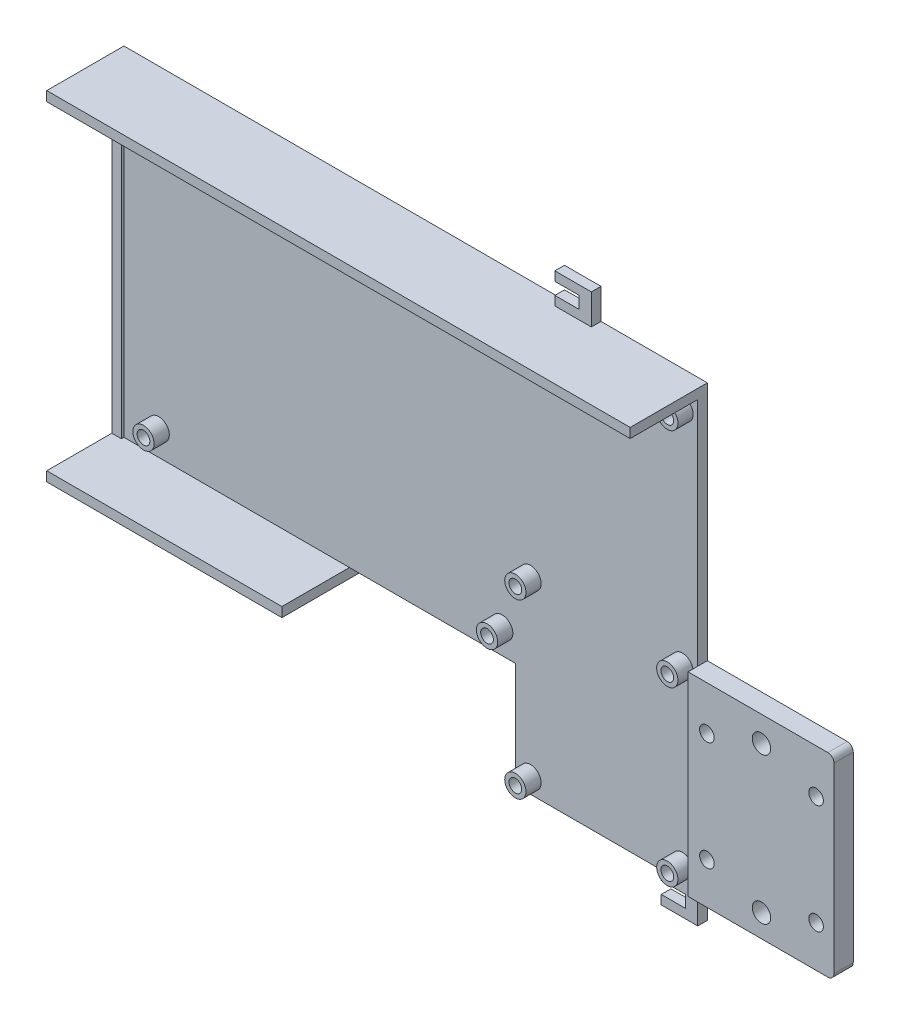
SolidWorks part; units mm, degrees
material "Custom Plastic"
ref_plane "X-Y Datum" through (0, 0, 0) normal (0, 0, 1) x (1, 0, 0)
ref_plane "X-Z Datum" through (0, 0, 0) normal (0, 1, 0) x (1, 0, 0)
ref_plane "Y-Z Datum" through (0, 0, 0) normal (1, 0, 0) x (0, 0, -1)
ref_plane "Plane1" through (-93.1675, 129.7126, -15.4932) normal (0, 1, 0) x (1, 0, 0)
sketch "Sketch2" plane through (0, 0, -17.0883) normal (0, 0, -1) x (-1, 0, 0)
  circle A0 centre (207.2845, 69.3586) radius 2.1 construction
  circle A1 centre (207.2845, 162.3226) radius 2.1 construction
  circle A2 centre (94.2545, 162.3226) radius 2.1 construction
  circle A3 centre (84.9365, 161.3866) radius 2.0955 construction
  circle A4 centre (94.2545, 69.3586) radius 2.1 construction
  circle A5 centre (84.9365, 88.1366) radius 2.0955 construction
  circle A6 centre (84.9365, 31.3866) radius 2.0955 construction
  circle A7 centre (34.9365, 31.3866) radius 2.0955 construction
  circle A8 centre (34.9365, 88.1366) radius 2.0955 construction
  circle A9 centre (34.9365, 161.3866) radius 2.0955 construction
  circle A10 centre (207.2845, 69.3586) radius 2.1
  circle A11 centre (207.2845, 162.3226) radius 2.1
  circle A12 centre (94.2545, 162.3226) radius 2.1
  circle A13 centre (84.9365, 161.3866) radius 2.0955
  circle A14 centre (94.2545, 69.3586) radius 2.1
  circle A15 centre (84.9365, 88.1366) radius 2.0955
  circle A16 centre (84.9365, 31.3866) radius 2.0955
  circle A17 centre (34.9365, 31.3866) radius 2.0955
  circle A18 centre (34.9365, 88.1366) radius 2.0955
  circle A19 centre (34.9365, 161.3866) radius 2.0955
  circle A20 centre (34.9365, 161.3866) radius 3.5
  circle A21 centre (84.9365, 161.3866) radius 3.5
  circle A22 centre (94.2545, 162.3226) radius 3.5
  circle A23 centre (207.2845, 162.3226) radius 3.5
  circle A24 centre (34.9365, 88.1366) radius 3.5
  circle A25 centre (34.9365, 31.3866) radius 3.5
  circle A26 centre (84.9365, 31.3866) radius 3.5
  circle A27 centre (84.9365, 88.1366) radius 3.5
  circle A28 centre (94.2545, 69.3586) radius 3.5
  circle A29 centre (207.2845, 69.3586) radius 3.5
  dimension "D1" = 7
  dimension "D2" = 7
  dimension "D3" = 7
  dimension "D4" = 7
extrude "Boss-Extrude1" add sketch "Sketch2" along normal blind 5
sketch "Sketch3" plane through (0, 0, -22.0883) normal (0, 0, -1) x (-1, 0, 0)
  line L1 (29.9365, 166.3866) -> (218.7145, 166.3866)
  line L2 (29.9365, 166.3866) -> (29.9365, 61.2306)
  line L3 (89.9365, 61.2306) -> (218.7145, 61.2306)
  line L4 (218.7145, 166.3866) -> (218.7145, 61.2306)
  line L6 (29.9365, 61.2306) -> (29.9365, 26.3866)
  line L7 (29.9365, 26.3866) -> (89.9365, 26.3866)
  line L8 (89.9365, 61.2306) -> (89.9365, 26.3866)
extrude "Boss-Extrude2" add sketch "Sketch3" along normal blind 3.175
sketch "Sketch4" plane through (0, 0, -25.2633) normal (0, 0, -1) x (-1, 0, 0)
  line L0 (29.9365, 166.3866) -> (29.9365, 169.5616)
  line L1 (144.5201, 58.0556) -> (144.5201, 61.2306)
  line L2 (89.9365, 61.2306) -> (218.7145, 61.2306) construction
  line L3 (218.7145, 166.3866) -> (221.8895, 166.3866)
  line L4 (218.7145, 61.2306) -> (221.8895, 61.2306)
  line L12 (26.7615, 169.5616) -> (26.7615, 23.2116)
  line L13 (26.7615, 23.2116) -> (93.1115, 23.2116)
  line L14 (93.1115, 23.2116) -> (93.1115, 58.0556)
  line L15 (93.1115, 58.0556) -> (221.8895, 58.0556)
  line L16 (221.8895, 58.0556) -> (221.8895, 169.5616)
  line L17 (221.8895, 169.5616) -> (26.7615, 169.5616)
  line L18 (26.7615, 169.5616) -> (26.7615, 23.2116)
  line L19 (26.7615, 23.2116) -> (93.1115, 23.2116)
  line L20 (93.1115, 23.2116) -> (93.1115, 58.0556)
  line L21 (93.1115, 58.0556) -> (221.8895, 58.0556)
  line L22 (221.8895, 58.0556) -> (221.8895, 169.5616)
  line L23 (221.8895, 169.5616) -> (26.7615, 169.5616)
  line M10 (89.9365, 61.2306) -> (218.7145, 61.2306)
  line M11 (218.7145, 61.2306) -> (218.7145, 166.3866)
  line M12 (218.7145, 166.3866) -> (29.9365, 166.3866)
  dimension "D1" = 3.175
extrude "Boss-Extrude3" add sketch "Sketch4" against normal blind 25.4 contours L22 L23 L18 L1 L21 M12 M11 M10 region at (-183.2048, 59.6431, -25.2633)
extrude "Boss-Extrude4" add sketch "Sketch4<3>" against normal blind 16 contours L21 L22 L4 L1 M10 region at (-183.2048, 59.6431, -25.2633)
sketch "Sketch4<3>" plane through (0, 0, -25.2633) normal (0, 0, -1) x (-1, 0, 0) same geometry as "Sketch4"
sketch "Sketch5" plane through (0, 0, -25.2633) normal (0, 0, -1) x (-1, 0, 0)
  line L0 (166.0515, 58.0556) -> (166.0515, 48.0556)
  line L1 (144.5201, 58.0556) -> (221.8895, 58.0556) construction
  line L2 (166.0515, 48.0556) -> (178.0515, 48.0556)
  line L3 (178.0515, 48.0556) -> (178.0515, 51.0556)
  line L4 (178.0515, 51.0556) -> (170.0515, 51.0556)
  line L5 (170.0515, 51.0556) -> (170.0515, 55.0556)
  line L6 (170.0515, 55.0556) -> (178.0515, 55.0556)
  line L7 (178.0515, 55.0556) -> (178.0515, 58.0556)
  line L8 (178.0515, 58.0556) -> (166.0515, 58.0556)
  line L9 (144.5201, 58.0556) -> (144.5201, 61.2306) construction
  dimension "D1" = 10
  dimension "D2" = 12
  dimension "D3" = 8
  dimension "D4" = 3
  dimension "D5" = 21.5314
extrude "Boss-Extrude5" add sketch "Sketch5" against normal blind 3.175
extrude "Boss-Extrude6" add sketch "Sketch4<4>" against normal blind 25.4 contours L22 L23 L0 L3 M12 region at (-125.913, 167.9741, -25.2633)
sketch "Sketch4<4>" plane through (0, 0, -25.2633) normal (0, 0, -1) x (-1, 0, 0) same geometry as "Sketch4"
extrude "Boss-Extrude7" add sketch "Sketch4<5>" against normal blind 4 contours L4 L22 L3 M11 region at (-220.302, 113.8086, -25.2633)
sketch "Sketch4<5>" plane through (0, 0, -25.2633) normal (0, 0, -1) x (-1, 0, 0) same geometry as "Sketch4"
sketch "Sketch6" plane through (0, 0, -25.2633) normal (0, 0, -1) x (-1, 0, 0)
  line L0 (125.913, 169.5616) -> (125.913, 61.2306)
  line L1 (221.8895, 169.5616) -> (29.9365, 169.5616) construction
  line L2 (89.9365, 61.2306) -> (144.5201, 61.2306) construction
  line L3 (145.913, 169.5616) -> (145.913, 179.5616)
  line L4 (145.913, 179.5616) -> (157.913, 179.5616)
  line L5 (157.913, 179.5616) -> (157.913, 176.5616)
  line L6 (157.913, 176.5616) -> (149.913, 176.5616)
  line L7 (149.913, 176.5616) -> (149.913, 172.5616)
  line L8 (149.913, 172.5616) -> (157.913, 172.5616)
  line L9 (157.913, 172.5616) -> (157.913, 169.5616)
  line L10 (157.913, 169.5616) -> (145.913, 169.5616)
  line L11 (64.9365, 179.5616) -> (64.9365, 169.5616)
  line L12 (64.9365, 169.5616) -> (76.9365, 169.5616)
  line L13 (76.9365, 169.5616) -> (76.9365, 172.5616)
  line L14 (76.9365, 172.5616) -> (68.9365, 172.5616)
  line L15 (68.9365, 172.5616) -> (68.9365, 176.5616)
  line L16 (68.9365, 176.5616) -> (76.9365, 176.5616)
  line L17 (76.9365, 176.5616) -> (76.9365, 179.5616)
  line L18 (76.9365, 179.5616) -> (64.9365, 179.5616)
  line L19 (29.9365, 169.5616) -> (29.9365, 26.3866) construction
  line L20 (29.9365, 26.3866) -> (29.9365, 16.3866)
  line L21 (29.9365, 16.3866) -> (41.9365, 16.3866)
  line L22 (41.9365, 16.3866) -> (41.9365, 19.3866)
  line L23 (41.9365, 19.3866) -> (33.9365, 19.3866)
  line L24 (33.9365, 19.3866) -> (33.9365, 23.3866)
  line L25 (33.9365, 23.3866) -> (41.9365, 23.3866)
  line L26 (41.9365, 23.3866) -> (41.9365, 26.3866)
  line L27 (29.9365, 26.3866) -> (89.9365, 26.3866) construction
  line L28 (41.9365, 26.3866) -> (29.9365, 26.3866)
  line M13 (221.8895, 169.5616) -> (29.9365, 169.5616)
  line M15 (29.9365, 26.3866) -> (89.9365, 26.3866)
  dimension "D11" = 10
  dimension "D1" = 35
  dimension "D2" = 3
  dimension "D3" = 10
  dimension "D4" = 12
  dimension "D5" = 8
  dimension "D6" = 20
  dimension "D7" = 12
  dimension "D8" = 8
  dimension "D9" = 10
  dimension "D10" = 3
  dimension "D12" = 3
  dimension "D13" = 12
  dimension "D14" = 8
extrude "Boss-Extrude8" add sketch "Sketch6" against normal blind 3.175 contours L17 L18 L11 L13 L14 L15 L16 M13 | L25 L26 L20 L21 L22 L23 L24 M15 region at (-70.9365, 169.7178, -25.2633) region at (-35.9365, 26.2304, -25.2633)
sketch "Sketch9" plane through (0, 0, -25.2633) normal (0, 0, -1) x (-1, 0, 0)
  line L0 (29.9365, 169.5616) -> (29.9365, 16.3866) construction
  line L1 (29.9365, 90.3866) -> (-18.0635, 90.3866)
  line L2 (29.9365, 90.3866) -> (29.9365, 26.3866)
  line L3 (29.9365, 26.3866) -> (-18.0635, 26.3866)
  line L4 (-18.0635, 90.3866) -> (-18.0635, 26.3866)
  line L6 (41.9365, 26.3866) -> (89.9365, 26.3866) construction
  dimension "D1" = 64
  dimension "D2" = 48
  dimension "D3" = 0
extrude "Boss-Extrude10" add sketch "Sketch9" against normal blind 6.35
sketch "Sketch10" plane through (0, 0, -18.9133) normal (0, 0, 1) x (1, 0, 0)
  circle A0 centre (12.1824, 75.9156) radius 2.4 construction
  circle A1 centre (-23.7386, 75.9156) radius 2.4 construction
  circle A2 centre (-23.7386, 39.9946) radius 2.4 construction
  circle A3 centre (12.1824, 39.9946) radius 2.4 construction
  circle A4 centre (12.1824, 75.9156) radius 2.4
  circle A5 centre (-23.7386, 75.9156) radius 2.4
  circle A6 centre (-23.7386, 39.9946) radius 2.4
  circle A7 centre (12.1824, 39.9946) radius 2.4
  circle A8 centre (-5.7781, 33.8672) radius 3.025 construction
  circle A9 centre (-5.7781, 82.0431) radius 3.025 construction
  circle A10 centre (-5.7781, 33.8672) radius 3.025
  circle A11 centre (-5.7781, 82.0431) radius 3.025
extrude "Cut-Extrude1" cut sketch "Sketch10" against normal blind 5
fillet "Fillet1" radius 2 3 edges at (18.0635, 90.3866, -22.0883) (18.0635, 26.3866, -22.0883) (-89.9365, 26.3866, -23.6758)
equation "\"16mmm\"=20"
